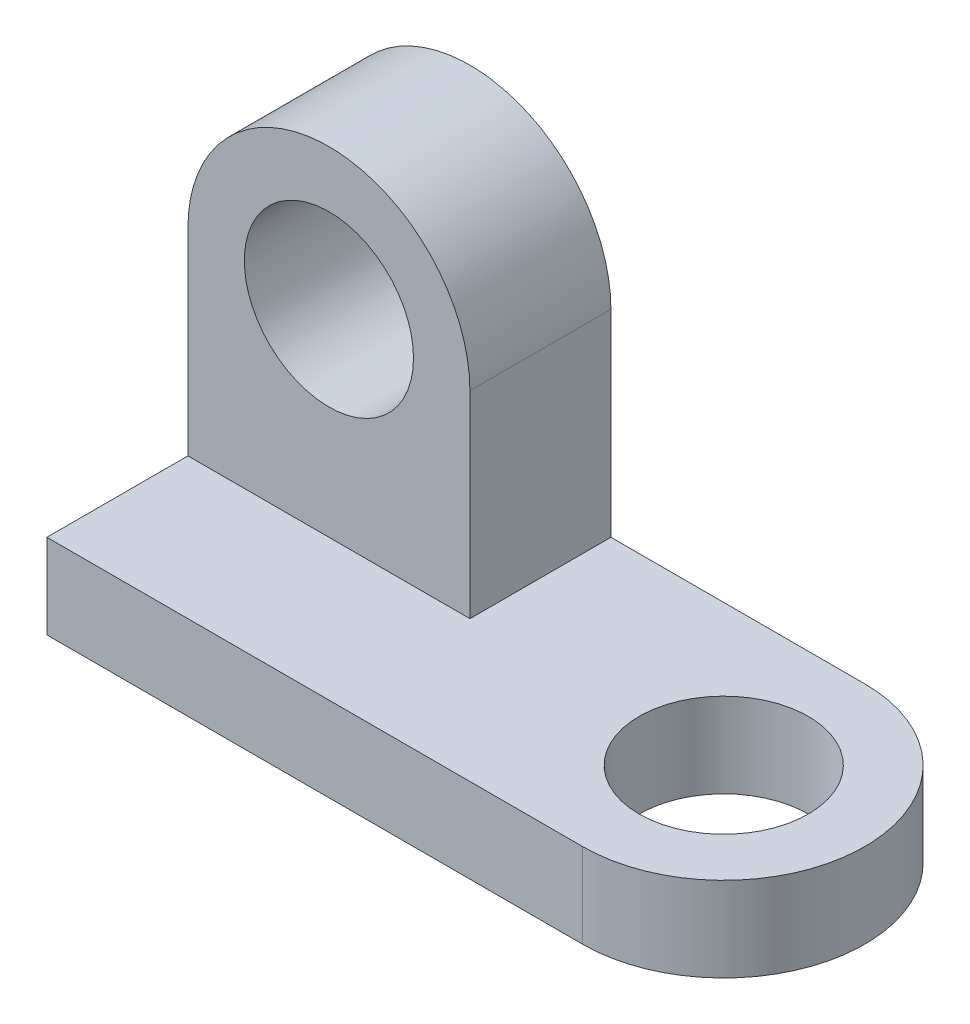
SolidWorks part; units mm, degrees
ref_plane "Alzado" through (0, 0, 0) normal (0, 0, 1) x (1, 0, 0)
ref_plane "Planta" through (0, 0, 0) normal (0, 1, 0) x (1, 0, 0)
ref_plane "Vista lateral" through (0, 0, 0) normal (1, 0, 0) x (0, 0, -1)
sketch "Croquis1" plane through (0, 0, 0) normal (0, 1, 0) x (1, 0, 0)
  line L1 (-60, 25) -> (60, 25)
  line L2 (-60, 25) -> (-60, -25)
  line L3 (-60, -25) -> (60, -25)
  line L4 (60, 25) -> (60, -25)
  line L5 (-60, 25) -> (60, -25) construction
  line L6 (-60, -25) -> (60, 25) construction
  point P0 (0, 0)
  dimension "D1" = 120
  dimension "D2" = 50
extrude "Saliente-Extruir1" add sketch "Croquis1" along normal blind 15
sketch "Croquis2" plane through (0, 15, 0) normal (0, 1, 0) x (1, 0, 0)
  line L1 (-60, 25) -> (-10, 25)
  line L2 (-60, 25) -> (-60, 0)
  line L3 (-60, 0) -> (-10, 0)
  line L4 (-10, 25) -> (-10, 0)
  dimension "D1" = 50
  dimension "D2" = 25
extrude "Saliente-Extruir2" add sketch "Croquis2" along normal blind 60
fillet "Redondeo5" 2 edges at (-60, 75, -12.5) (-10, 75, -12.5) type full round first side face at (-60, 35, -2.0833) second side face at (-10, 52.5, -9.375) middle face at (-35, 75, -12.5)
fillet "Redondeo6" 2 edges at (60, 7.5, 25) (60, 7.5, -25) type full round first side face at (0, 7.5, 25) second side face at (2.5, 28.75, -25) middle face at (60, 7.5, 0)
sketch "Croquis3" plane through (0, 15, 0) normal (0, 1, 0) x (1, 0, 0)
  circle A0 centre (35, 0) radius 15
  arc A1 (35, -25) -> (35, 25) centre (35, 0) ccw construction
  dimension "D1" = 30
extrude "Cortar-Extruir1" cut sketch "Croquis3" against normal through all
sketch "Croquis4" plane through (0, 0, 0) normal (0, 0, 1) x (1, 0, 0)
  circle A0 centre (-35, 50) radius 15
  arc A1 (-10, 50) -> (-60, 50) centre (-35, 50) ccw construction
  dimension "D1" = 30
extrude "Cortar-Extruir2" cut sketch "Croquis4" against normal through all contours A0
